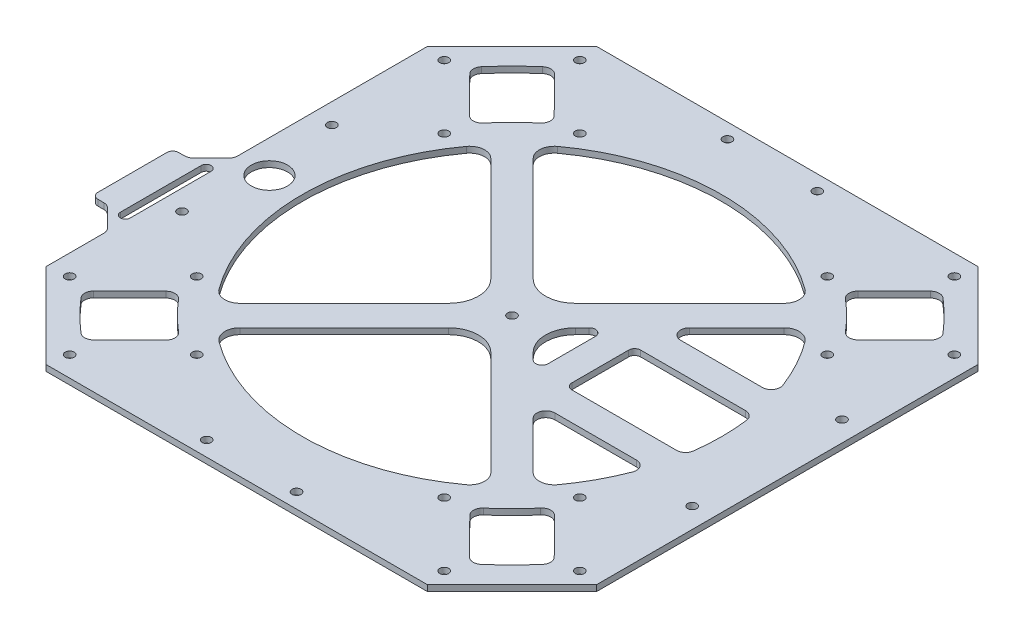
SolidWorks part; units mm, degrees
material "Thornel Mat VMA"
ref_plane "前视基准面" through (0, 0, 0) normal (0, 0, 1) x (1, 0, 0)
ref_plane "上视基准面" through (0, 0, 0) normal (0, 1, 0) x (1, 0, 0)
ref_plane "右视基准面" through (0, 0, 0) normal (1, 0, 0) x (0, 0, -1)
sketch "草图1" plane through (0, 0, 0) normal (0, 1, 0) x (1, 0, 0)
  line L0 (-63.6396, 91.9239) -> (-91.9239, 63.6396)
  line L1 (63.6396, 91.9239) -> (-63.6396, 91.9239)
  line L2 (91.9239, 63.6396) -> (91.9239, -63.6396)
  line L3 (63.6396, -91.9239) -> (-63.6396, -91.9239)
  line L4 (-91.9239, 63.6396) -> (-91.9239, -63.6396)
  line L5 (91.9239, 91.9239) -> (-91.9239, -91.9239) construction
  line L6 (91.9239, -91.9239) -> (-91.9239, 91.9239) construction
  line L7 (91.9239, -63.6396) -> (63.6396, -91.9239)
  line L8 (-91.9239, -63.6396) -> (-63.6396, -91.9239)
  line L9 (63.6396, 91.9239) -> (91.9239, 63.6396)
  line L10 (-91.9239, 91.9239) -> (-91.9239, -91.9239) construction
  line L11 (-91.9239, -91.9239) -> (91.9239, -91.9239) construction
  line L12 (91.9239, -91.9239) -> (91.9239, 91.9239) construction
  line L13 (91.9239, 91.9239) -> (-91.9239, 91.9239) construction
  point P0 (0, 0)
  dimension "D1" = 220
  dimension "D2" = 40
extrude "凸台-拉伸1" add sketch "草图1" along normal blind 2
sketch "草图11" plane through (0, 2, 0) normal (0, 1, 0) x (1, 0, 0)
  circle A0 centre (0, 0) radius 70
  dimension "D1" = 140
extrude "切除-拉伸6" cut sketch "草图11" against normal through all both and the other way through all
hole_wizard "孔1" positions "草图13" profile "草图14" legacy end condition through all
sketch "草图13" plane through (0, 0, 0) normal (0, -1, 0) x (-1, 0, 0)
  point P0 (85.1534, -62.5223)
  point P3 (63.9402, -41.3091)
  point P6 (41.3127, -63.9365)
  point P9 (62.5259, -85.1497)
  point P12 (-62.5259, -85.1497)
  point P15 (-41.3127, -63.9365)
  point P18 (-63.9402, -41.3091)
  point P21 (-85.1534, -62.5223)
  point P24 (-85.1534, 62.5296)
  point P27 (-62.5259, 85.157)
  point P30 (-41.3127, 63.9438)
  point P33 (-63.9402, 41.3164)
  point P36 (85.1534, 62.5296)
  point P39 (63.9402, 41.3164)
  point P42 (41.3127, 63.9438)
  point P45 (62.5259, 85.157)
sketch "草图14" plane through (-85.1534, 0, 62.5223) normal (1, 0, 0) x (0, 0, -1)
  line L0 (0, 0) -> (0, 2)
  line L1 (0, 2) -> (1.5, 2)
  line L2 (1.5, 2) -> (1.5, 0)
  line L3 (1.5, 0) -> (0, 0)
  line L4 (0, 110) -> (0, -10) construction
  dimension "直径" = 3
  dimension "深度" = 2
sketch "草图15" plane through (0, 2, 0) normal (0, 1, 0) x (1, 0, 0)
  line L0 (-54.5847, 45.4949) -> (-58.1891, 38.9105)
  line L1 (42.968, -57.1116) -> (54.5847, -45.4949)
  line L2 (-42.968, 57.1116) -> (-34.497, 60.9094)
  line L3 (57.1116, 42.968) -> (60.9094, 34.497)
  line L4 (57.1116, 42.968) -> (45.4949, 54.5847)
  line L5 (45.4949, 54.5847) -> (38.9105, 58.1891)
  line L6 (42.968, -57.1116) -> (34.497, -60.9094)
  line L7 (42.968, -57.1116) -> (54.5847, -45.4949)
  line L8 (-57.1116, -42.968) -> (-45.4949, -54.5847)
  line L9 (54.5847, -45.4949) -> (58.1891, -38.9105)
  line L10 (-57.1116, -42.968) -> (-60.9094, -34.497)
  line L11 (-57.1116, -42.968) -> (-45.4949, -54.5847)
  line L12 (-45.4949, -54.5847) -> (-38.9105, -58.1891)
  line L14 (-42.968, 57.1116) -> (-54.5847, 45.4949)
  line L20 (57.1116, 42.968) -> (45.4949, 54.5847)
  line L27 (-14.1421, 7.0711) -> (-48.9503, 41.8792)
  line L30 (-14.1421, -7.0711) -> (-48.9503, -41.8792)
  line L31 (7.0711, 14.1421) -> (41.8792, 48.9503)
  line L33 (-7.0711, 14.1421) -> (-41.8792, 48.9503)
  line L36 (14.1421, -7.0711) -> (48.9503, -41.8792)
  line L42 (7.0711, -14.1421) -> (41.8792, -48.9503)
  line L48 (-7.0711, -14.1421) -> (-41.8792, -48.9503)
  line L49 (14.1421, 7.0711) -> (48.9503, 41.8792)
  arc A0 (-56.5232, 41.2932) -> (-58.1891, 38.9105) centre (0, 0) ccw
  arc A1 (-34.497, 60.9094) -> (-41.2932, 56.5232) centre (0, 0) ccw
  arc A2 (-41.2932, -56.5232) -> (-38.9105, -58.1891) centre (0, 0) ccw
  arc A3 (60.9094, 34.497) -> (56.5232, 41.2932) centre (0, 0) ccw
  arc A4 (41.2932, 56.5232) -> (38.9105, 58.1891) centre (0, 0) ccw
  arc A5 (34.497, -60.9094) -> (41.2932, -56.5232) centre (0, 0) ccw
  arc A6 (56.5232, -41.2932) -> (58.1891, -38.9105) centre (0, 0) ccw
  arc A7 (-60.9094, -34.497) -> (-56.5232, -41.2932) centre (0, 0) ccw
  arc A8 (-45.8355, -52.9066) -> (-38.9105, -58.1891) centre (0, 0) ccw
  arc A9 (60.9094, 34.497) -> (52.9066, 45.8355) centre (0, 0) ccw
  arc A10 (34.497, -60.9094) -> (45.8355, -52.9066) centre (0, 0) ccw
  arc A11 (52.9066, -45.8355) -> (58.1891, -38.9105) centre (0, 0) ccw
  arc A12 (7.0711, -14.1421) -> (-7.0711, -14.1421) centre (0, -21.2132) ccw
  arc A13 (14.1421, -7.0711) -> (14.1421, 7.0711) centre (21.2132, 0) cw
  arc A14 (7.0711, 14.1421) -> (-7.0711, 14.1421) centre (0, 21.2132) cw
  arc A15 (-14.1421, -7.0711) -> (-14.1421, 7.0711) centre (-21.2132, 0) ccw
  circle A16 centre (0, 0) radius 70 construction
  arc A17 (56.5232, -41.2932) -> (48.9503, -41.8792) centre (52.4858, -38.3437) cw
  arc A18 (41.8792, -48.9503) -> (41.2932, -56.5232) centre (38.3437, -52.4858) cw
  arc A19 (56.5232, 41.2932) -> (48.9503, 41.8792) centre (52.4858, 38.3437) ccw
  arc A20 (41.2932, 56.5232) -> (41.8792, 48.9503) centre (38.3437, 52.4858) cw
  arc A21 (-41.2932, 56.5232) -> (-41.8792, 48.9503) centre (-38.3437, 52.4858) ccw
  arc A22 (-48.9503, 41.8792) -> (-56.5232, 41.2932) centre (-52.4858, 38.3437) ccw
  arc A23 (-41.8792, -48.9503) -> (-41.2932, -56.5232) centre (-38.3437, -52.4858) ccw
  arc A24 (-48.9503, -41.8792) -> (-56.5232, -41.2932) centre (-52.4858, -38.3437) cw
  point P1 (0, 0)
  point P11 (0, 0)
  point P16 (0, 0)
  point P21 (0, 0)
  point P58 (0, 0)
  circle M25 centre (0, 0) radius 70
  dimension "D1" = 10
  dimension "D4" = 5
  dimension "D2" = 4
  dimension "D3" = 4
extrude "凸台-拉伸5" add sketch "草图15" against normal up to surface (2 mm away) contours A15 L30 L48 A12 L42 L36 A13 L49 L31 A14 L33 L27 M25 | L8 L12 L10 M25 | L1 L9 L6 M25 | L4 L5 L3 M25 | L2 L14 L0 M25 region at (-47.2019, 2, -51.7628) region at (0, 2, 0) region at (-51.7628, 2, 47.2019) region at (51.7628, 2, -47.2019) region at (47.2019, 2, 51.7628) up to face at (-85.1534, 0, 61.0223)
hole_wizard "孔2" positions "草图16" profile "草图17" legacy end condition through all
sketch "草图16" plane through (0, 0, 0) normal (0, -1, 0) x (-1, 0, 0)
  point P0 (0, 0)
sketch "草图17" plane through (0, 0, 0) normal (1, 0, 0) x (0, 0, -1)
  line L0 (0, 0) -> (0, 2)
  line L1 (0, 2) -> (1.5, 2)
  line L2 (1.5, 2) -> (1.5, 0)
  line L3 (1.5, 0) -> (0, 0)
  line L4 (0, 110) -> (0, -10) construction
  dimension "直径" = 3
  dimension "深度" = 2
sketch "草图20" plane through (0, 2, 0) normal (0, 1, 0) x (1, 0, 0)
  line L0 (55.8614, 55.8614) -> (77.7817, 77.7817) construction
  line L1 (64.8107, 50.7195) -> (76.9107, 62.7268)
  line L3 (50.7195, -64.8107) -> (62.7268, -76.9107)
  line L4 (50.6805, 64.8737) -> (62.7878, 76.8882)
  line L5 (62.453, 48.3799) -> (64.7375, 78.823) construction
  line L6 (78.8741, 64.6752) -> (48.3019, 62.5134) construction
  line L7 (64.8737, -50.6805) -> (76.8882, -62.7878)
  line L8 (55.8614, -55.8614) -> (77.7817, -77.7817) construction
  line L9 (48.3799, -62.453) -> (78.823, -64.7375) construction
  line L10 (64.6752, -78.8741) -> (62.5134, -48.3019) construction
  line L11 (-64.8107, -50.7195) -> (-76.9107, -62.7268)
  line L12 (-50.6805, -64.8737) -> (-62.7878, -76.8882)
  line L13 (-55.8614, -55.8614) -> (-77.7817, -77.7817) construction
  line L14 (-62.453, -48.3799) -> (-64.7375, -78.823) construction
  line L15 (-78.8741, -64.6752) -> (-48.3019, -62.5134) construction
  line L16 (-50.7195, 64.8107) -> (-62.7268, 76.9107)
  line L17 (-64.8737, 50.6805) -> (-76.8882, 62.7878)
  line L18 (-55.8614, 55.8614) -> (-77.7817, 77.7817) construction
  line L19 (-48.3799, 62.453) -> (-78.823, 64.7375) construction
  line L20 (-64.6752, 78.8741) -> (-62.5134, 48.3019) construction
  line L21 (91.9239, 63.6396) -> (63.6396, 91.9239) construction
  arc A0 (77.0641, 66.8216) -> (66.8676, 77.0242) centre (0, 0) ccw
  arc A1 (60.4037, 50.9155) -> (50.8621, 60.4487) centre (0, 0) ccw
  arc A3 (64.8107, 50.7195) -> (60.4037, 50.9155) centre (62.6976, 52.849) cw
  arc A4 (76.9107, 62.7268) -> (77.0641, 66.8216) centre (74.7975, 64.8562) ccw
  arc A5 (66.8676, 77.0242) -> (62.7878, 76.8882) centre (64.9009, 74.7588) ccw
  arc A6 (50.8621, 60.4487) -> (50.6805, 64.8737) centre (52.7936, 62.7442) cw
  arc A7 (66.8216, -77.0641) -> (77.0242, -66.8676) centre (0, 0) ccw
  arc A8 (50.9155, -60.4037) -> (60.4487, -50.8621) centre (0, 0) ccw
  arc A9 (50.7195, -64.8107) -> (50.9155, -60.4037) centre (52.849, -62.6976) cw
  arc A10 (62.7268, -76.9107) -> (66.8216, -77.0641) centre (64.8562, -74.7975) ccw
  arc A11 (77.0242, -66.8676) -> (76.8882, -62.7878) centre (74.7588, -64.9009) ccw
  arc A12 (60.4487, -50.8621) -> (64.8737, -50.6805) centre (62.7442, -52.7936) cw
  arc A13 (-77.0641, -66.8216) -> (-66.8676, -77.0242) centre (0, 0) ccw
  arc A14 (-60.4037, -50.9155) -> (-50.8621, -60.4487) centre (0, 0) ccw
  arc A15 (-64.8107, -50.7195) -> (-60.4037, -50.9155) centre (-62.6976, -52.849) cw
  arc A16 (-76.9107, -62.7268) -> (-77.0641, -66.8216) centre (-74.7975, -64.8562) ccw
  arc A17 (-66.8676, -77.0242) -> (-62.7878, -76.8882) centre (-64.9009, -74.7588) ccw
  arc A18 (-50.8621, -60.4487) -> (-50.6805, -64.8737) centre (-52.7936, -62.7442) cw
  arc A19 (-66.8216, 77.0641) -> (-77.0242, 66.8676) centre (0, 0) ccw
  arc A20 (-50.9155, 60.4037) -> (-60.4487, 50.8621) centre (0, 0) ccw
  arc A21 (-50.7195, 64.8107) -> (-50.9155, 60.4037) centre (-52.849, 62.6976) cw
  arc A22 (-62.7268, 76.9107) -> (-66.8216, 77.0641) centre (-64.8562, 74.7975) ccw
  arc A23 (-77.0242, 66.8676) -> (-76.8882, 62.7878) centre (-74.7588, 64.9009) ccw
  arc A24 (-60.4487, 50.8621) -> (-64.8737, 50.6805) centre (-62.7442, 52.7936) cw
  point P4 (0, 0)
  point P5 (63.5947, 63.5947)
  point P23 (0, 0)
  point P24 (77.7817, 77.7817)
  point P26 (63.5947, -63.5947)
  point P45 (-63.5947, -63.5947)
  point P64 (-63.5947, 63.5947)
  point P82 (0, 0)
  dimension "D1" = 79
  dimension "D2" = 102
  dimension "D4" = 3
  dimension "D3" = 20
  dimension "D5" = 4
extrude "切除-拉伸7" cut sketch "草图20" against normal through all both and the other way through all
sketch "草图21" plane through (0, 2, 0) normal (0, 1, 0) x (1, 0, 0)
  line L0 (-91.9239, 0) -> (-70, 0) construction
  line L1 (-91.9239, 63.6396) -> (-91.9239, -63.6396) construction
  circle A0 centre (-80.9686, 0) radius 6.05
  arc A1 (-56.5232, 41.2932) -> (-56.5232, -41.2932) centre (0, 0) ccw construction
  point P9 (0, 0)
  dimension "D1" = 12.1
extrude "切除-拉伸8" cut sketch "草图21" against normal through all both and the other way through all
sketch "草图22" plane through (0, 2, 0) normal (0, 1, 0) x (1, 0, 0)
  line L0 (0, 91.9239) -> (0, -91.9239) construction
  line L1 (63.6396, 91.9239) -> (-63.6396, 91.9239) construction
  line L2 (-63.6396, -91.9239) -> (63.6396, -91.9239) construction
  line L3 (85.1534, 62.5296) -> (85.1534, -62.5223) construction
  line L4 (15, 86.9239) -> (-15, 86.9239)
  line L5 (15, 86.9239) -> (15, -86.9239)
  line L6 (15, -86.9239) -> (-15, -86.9239)
  line L7 (-15, 86.9239) -> (-15, -86.9239)
  line L8 (15, 86.9239) -> (-15, -86.9239) construction
  line L9 (15, -86.9239) -> (-15, 86.9239) construction
  line L10 (-85.1534, 25) -> (85.1534, 25)
  line L11 (-85.1534, 25) -> (-85.1534, -25)
  line L12 (-85.1534, -25) -> (85.1534, -25)
  line L13 (85.1534, 25) -> (85.1534, -25)
  line L14 (-85.1534, 25) -> (85.1534, -25) construction
  line L15 (-85.1534, -25) -> (85.1534, 25) construction
  point P6 (0, 0)
  point P12 (0, 0)
  point P22 (85.1534, -18.4563)
  dimension "D1" = 30
  dimension "D2" = 5
  dimension "D3" = 50
hole_wizard "孔4" positions "草图23" profile "草图24" legacy end condition through all
sketch "草图23" plane through (0, 2, 0) normal (0, 1, 0) x (1, 0, 0)
  point P0 (-15, -86.9239)
  point P3 (15, -86.9239)
  point P6 (-15, 86.9239)
  point P9 (15, 86.9239)
  point P12 (-85.1534, 25)
  point P15 (-85.1534, -25)
  point P18 (85.1534, 25)
  point P21 (85.1534, -25)
sketch "草图24" plane through (-15, 2, 86.9239) normal (1, 0, 0) x (0, 0, 1)
  line L0 (0, 0) -> (0, 2)
  line L1 (0, 2) -> (1.5, 2)
  line L2 (1.5, 2) -> (1.5, 0)
  line L3 (1.5, 0) -> (0, 0)
  line L4 (0, 110) -> (0, -10) construction
  dimension "直径" = 3
  dimension "深度" = 2
sketch "草图25" plane through (0, 0, 0) normal (0, -1, 0) x (-1, 0, 0)
  line L0 (-35.3137, -21) -> (-62.554, -21)
  line L1 (-48.9503, -41.8792) -> (-14.1421, -7.0711) construction
  line L2 (-22.95, -21) -> (-81.05, -21) construction
  line L3 (-35.5633, 28.4923) -> (-33.1924, 26.1213)
  line L4 (-66.4586, -11.5) -> (-31.45, -11.5)
  line L5 (-16.4055, -9.3344) -> (-14.021, -6.9499)
  line L6 (-14.021, -6.9499) -> (-12.0262, -9.8724)
  line L7 (-12.0262, -9.8724) -> (-34.9991, -29.1641)
  line L8 (-34.9991, -29.1641) -> (-35.5633, -28.4923)
  line L9 (-35.5633, -28.4923) -> (-33.1924, -26.1213)
  line L10 (0, 0) -> (-75.6878, 0) construction
  line L11 (-34.9991, 29.1641) -> (-35.5633, 28.4923)
  line L12 (-12.0262, 9.8724) -> (-34.9991, 29.1641)
  line L13 (-14.021, 6.9499) -> (-12.0262, 9.8724)
  line L14 (-16.4055, 9.3344) -> (-14.021, 6.9499)
  line L15 (-66.4586, 11.5) -> (-31.45, 11.5)
  line L16 (-35.3137, 21) -> (-62.554, 21)
  line L17 (-19.95, 7.8662) -> (-19.95, -7.8662)
  line L18 (-19.95, 18) -> (-19.95, -18) construction
  line L20 (-29.45, -9.5) -> (-29.45, 9.5)
  arc A0 (-65.3549, 25.0746) -> (-69.4344, 8.8806) centre (0, 0) ccw
  arc A1 (-56.5232, 41.2932) -> (-56.5232, -41.2932) centre (0, 0) ccw construction
  arc A2 (-31.45, 11.5) -> (-29.45, 9.5) centre (-31.45, 9.5) cw
  arc A3 (-35.3137, -21) -> (-33.1924, -26.1213) centre (-35.3137, -24) cw
  arc A4 (-69.4344, -8.8806) -> (-66.4586, -11.5) centre (-66.4586, -8.5) ccw
  arc A5 (-65.3549, -25.0746) -> (-62.554, -21) centre (-62.554, -24) cw
  arc A6 (-65.3549, 25.0746) -> (-62.554, 21) centre (-62.554, 24) ccw
  arc A7 (-69.4344, 8.8806) -> (-66.4586, 11.5) centre (-66.4586, 8.5) cw
  arc A8 (-35.3137, 21) -> (-33.1924, 26.1213) centre (-35.3137, 24) ccw
  arc A9 (-31.45, -11.5) -> (-29.45, -9.5) centre (-31.45, -9.5) ccw
  arc A10 (-16.4055, 9.3344) -> (-19.95, 7.8662) centre (-17.8737, 7.8662) ccw
  arc A11 (-19.95, -7.8662) -> (-16.4055, -9.3344) centre (-17.8737, -7.8662) ccw
  arc A12 (-65.3549, 25.0746) -> (-69.4344, 8.8806) centre (0, 0) ccw
  arc A13 (-69.4344, -8.8806) -> (-65.3549, -25.0746) centre (0, 0) ccw
  point P18 (-18.5711, -11.5)
  point P21 (-28.0711, -21)
  point P42 (-28.0711, 21)
  point P43 (-18.5711, 11.5)
  point P48 (-29.45, 11.5)
  point P51 (-29.45, -11.5)
  point P56 (-19.95, 12.8789)
  point P59 (-19.95, -12.8789)
  dimension "D1" = 9.5
  dimension "D3" = 2
  dimension "D4" = 2.0763
  dimension "D2" = 9.5
extrude "凸台-拉伸6" add sketch "草图25" against normal blind 2 contours L17 L10 L20 A9 L4 A4 A13 A5 L0 A3 L9 L8 L7 L6 L5 A11 | L10 L17 A10 L14 L13 L12 L11 L3 A8 L16 A6 A0 A7 L15 A2 L20 region at (39.1292, 0, 14.3852) region at (39.1292, 0, -14.3852)
sketch "草图26" plane through (0, 0, 0) normal (0, -1, 0) x (-1, 0, 0)
  line L0 (102.75, -8.4964) -> (100.7846, -8.4964)
  line L1 (91.9239, 63.6396) -> (91.9239, -63.6396) construction
  line L2 (104.75, -33.4964) -> (104.75, -10.4964)
  line L3 (98.6633, -7.6177) -> (92.8026, -1.757)
  line L4 (91.9239, 0.3643) -> (91.9239, 14.8019)
  line L5 (91.9239, 14.8019) -> (89.0707, 14.8019)
  line L6 (89.0707, 14.8019) -> (89.0707, -56.1873)
  line L7 (89.0707, -56.1873) -> (91.9239, -56.1873)
  line L8 (91.9239, -56.1873) -> (91.9239, -44.3571)
  line L9 (91.9239, -35.4964) -> (104.75, -35.4964) construction
  line L10 (104.75, -35.4964) -> (104.75, -8.4964) construction
  line L11 (104.75, -8.4964) -> (94.8549, -8.4964) construction
  line L12 (93.5869, -35.4964) -> (93.5869, -8.4964) construction
  line L13 (91.9239, -35.4964) -> (91.9239, -8.4964)
  line L14 (95.25, -35.4964) -> (95.25, -8.4964)
  line L15 (93.5869, -21.9964) -> (104.75, -21.9964) construction
  line L16 (93.5869, -35.4964) -> (96.65, -40.6556) construction
  line L17 (91.9239, 63.6396) -> (91.9239, -63.6396) construction
  line L18 (102.75, -35.4964) -> (100.7846, -35.4964)
  line L19 (98.6633, -36.3751) -> (92.8026, -42.2358)
  line L20 (99.542, -8.4964) -> (99.542, -35.4964) construction
  arc A0 (98.6633, -36.3751) -> (100.7846, -35.4964) centre (100.7846, -38.4964) cw
  arc A1 (100.7846, -8.4964) -> (98.6633, -7.6177) centre (100.7846, -5.4964) cw
  arc A2 (91.9239, 0.3643) -> (92.8026, -1.757) centre (94.9239, 0.3643) ccw
  arc A3 (92.8026, -42.2358) -> (91.9239, -44.3571) centre (94.9239, -44.3571) ccw
  arc A4 (91.9239, -35.4964) -> (95.25, -35.4964) centre (93.5869, -35.4964) ccw
  arc A5 (95.25, -8.4964) -> (91.9239, -8.4964) centre (93.5869, -8.4964) ccw
  arc A6 (102.75, -35.4964) -> (104.75, -33.4964) centre (102.75, -33.4964) ccw
  arc A7 (104.75, -10.4964) -> (102.75, -8.4964) centre (102.75, -10.4964) ccw
  point P1 (93.5869, -21.9964)
  point P4 (93.5869, -8.4964)
  point P23 (91.9239, -48.3225)
  point P24 (99.5104, -34.8925)
  point P26 (91.9239, 4.3297)
  point P40 (91.9239, -0.8783)
  point P43 (91.9239, -43.1145)
  dimension "D1" = 3
  dimension "D2" = 2
  dimension "D4" = 9.5
  dimension "D5" = 6
extrude "凸台-拉伸7" add sketch "草图26" against normal blind 2
